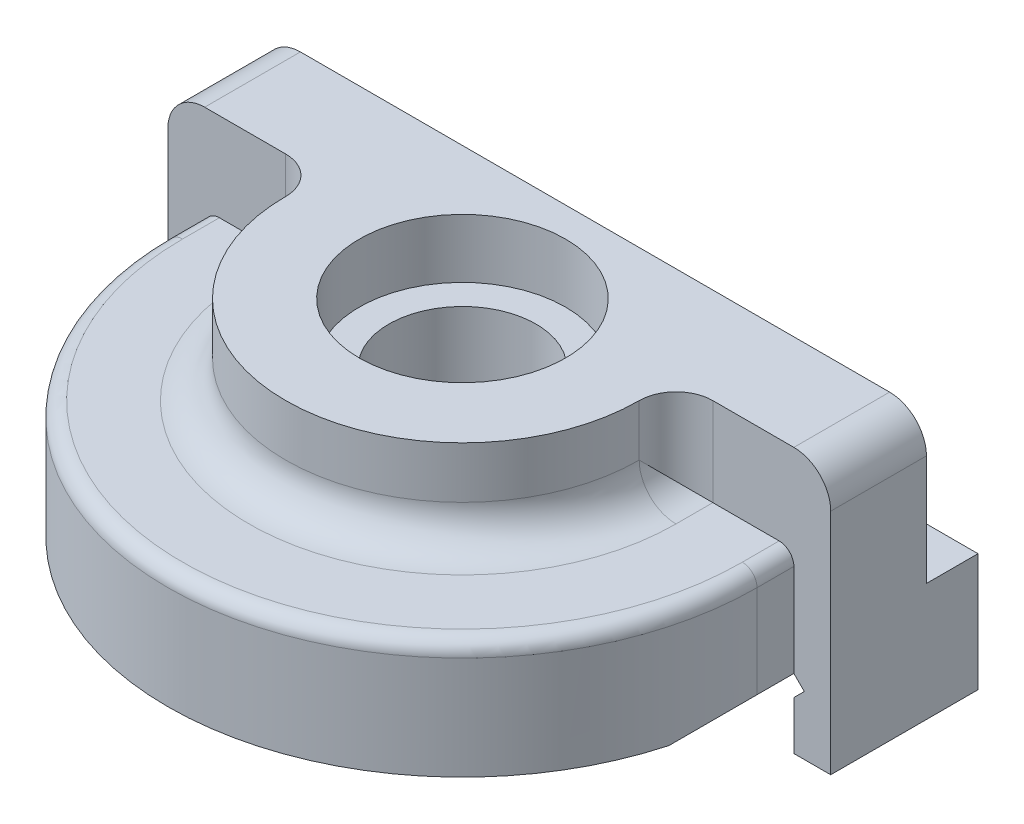
SolidWorks part; units mm, degrees
material "HT200"
ref_plane "前视基准面" through (0, 0, 0) normal (0, 0, 1) x (1, 0, 0)
ref_plane "上视基准面" through (0, 0, 0) normal (0, 1, 0) x (1, 0, 0)
ref_plane "右视基准面" through (0, 0, 0) normal (1, 0, 0) x (0, 0, -1)
sketch "草图1" plane through (0, 0, 0) normal (0, 1, 0) x (1, 0, 0)
  line L0 (0, 63.0153) -> (0, -95.916) construction
  line L1 (-48.6876, 0) -> (44.973, 0) construction
  line L2 (40, 5) -> (-40, 5)
  line L3 (-40, 5) -> (-40, 0)
  line L4 (40, 5) -> (40, 0)
  arc A0 (-40, 0) -> (40, 0) centre (0, 0) ccw
  point P11 (0, 5)
  dimension "D1" = 40
  dimension "D2" = 5
extrude "凸台-拉伸1" add sketch "草图1" along normal blind 16
sketch "草图3" plane through (0, 16, 0) normal (0, 1, 0) x (1, 0, 0)
  line L0 (-24, 5) -> (-24, 0)
  line L1 (40, 5) -> (-40, 5) construction
  line L2 (0, 7.0217) -> (0, -32.5675) construction
  line L3 (24, 5) -> (24, 0)
  line L4 (24, 5) -> (-24, 5)
  arc A0 (-24, 0) -> (24, 0) centre (0, 0) ccw
  dimension "D1" = 24
extrude "凸台-拉伸2" add sketch "草图3" along normal blind 12
sketch "草图4" plane through (0, 0, -5) normal (0, 0, -1) x (-1, 0, 0)
  line L0 (-45, 23) -> (-45, -8)
  line L1 (-45, -8) -> (-40, -8)
  line L2 (-40, 16) -> (-40, 0) construction
  line L3 (-40, 0) -> (-40, -8)
  line L4 (-40.9073, 0.8846) -> (-39.2434, -0.7794) construction
  line L5 (40, 0) -> (40, -8)
  line L6 (0, -3.1778) -> (0, 36.749) construction
  line L7 (45, -8) -> (40, -8)
  line L8 (-40, 0) -> (40, 0)
  line L9 (40, 0) -> (40, 16)
  line L10 (40, 16) -> (24, 16)
  line L11 (24, 16) -> (24, 28)
  line L12 (24, 28) -> (-24, 28)
  line L13 (-24, 28) -> (-24, 16)
  line L14 (-24, 16) -> (-40, 16)
  line L15 (-40, 16) -> (-40, 0)
  line L16 (-40, 0) -> (40, 0)
  line L17 (45, 23) -> (45, -8)
  line L19 (-39.994, -0.8169) -> (-40.006, 0.8169) construction
  line L20 (40, 28) -> (-40, 28)
  arc A0 (45, 23) -> (40, 28) centre (40, 23) ccw
  arc A1 (-45, 23) -> (-40, 28) centre (-40, 23) cw
  point P22 (0, 28)
  point P24 (45, 28)
  point P27 (-45, 28)
  dimension "D4" = 5
  dimension "D2" = 36
  dimension "D3" = 90
  dimension "D1" = 0
extrude "凸台-拉伸3" add sketch "草图4" along normal blind 20
sketch "草图5" plane through (0, 0, -25) normal (0, 0, -1) x (-1, 0, 0)
  line L0 (-45, 8) -> (45, 8)
  line L8 (-40, 0) -> (40, 0)
  line L9 (40, 0) -> (40, -8)
  line L10 (40, -8) -> (45, -8)
  line L11 (45, -8) -> (45, 23)
  line L12 (40, 28) -> (-40, 28)
  line L13 (-45, 23) -> (-45, -8)
  line L14 (-45, -8) -> (-40, -8)
  line L15 (-40, -8) -> (-40, 0)
  line L19 (45, 8) -> (45, 23)
  line L20 (40, 28) -> (-40, 28)
  line L21 (-45, 23) -> (-45, 8)
  arc A2 (45, 23) -> (40, 28) centre (40, 23) ccw
  arc A3 (-40, 28) -> (-45, 23) centre (-40, 23) ccw
  arc A4 (45, 23) -> (40, 28) centre (40, 23) ccw
  arc A5 (-40, 28) -> (-45, 23) centre (-40, 23) ccw
  dimension "D2" = 20
  dimension "D1" = 0
extrude "切除-拉伸1" cut sketch "草图5" against normal blind 7
sketch "草图6" plane through (0, 28, 0) normal (0, 1, 0) x (1, 0, 0)
  circle A0 centre (0, 0) radius 10
  dimension "D1" = 20
extrude "切除-拉伸2" cut sketch "草图6" against normal through all
sketch "草图7" plane through (0, 28, 0) normal (0, 1, 0) x (1, 0, 0)
  circle A0 centre (0, 0) radius 14
  dimension "D1" = 28
extrude "切除-拉伸3" cut sketch "草图7" against normal blind 8
sketch "草图9" plane through (0, 0, -18) normal (0, 0, -1) x (-1, 0, 0)
  line L0 (0, -1.4431) -> (0, 32.2689) construction
  line L1 (-45, 8) -> (45, 8) construction
  point P3 (-20, 19)
  point P4 (20, 19)
  dimension "D1" = 40
  dimension "D2" = 11
hole_wizard "M8 螺纹孔1" positions "草图11" profile "草图10" tap size "M8" standard "GB"
sketch "草图11" plane through (0, 0, -18) normal (0, 0, -1) x (-1, 0, 0)
  point P0 (-20, 19)
  point P1 (20, 19)
sketch "草图10" plane through (20, 19, -18) normal (1, 0, 0) x (0, 1, 0)
  line L0 (0, 0) -> (0, 18.2929)
  line L1 (0, 18.2929) -> (3.4, 16.25)
  line L2 (3.4, 16.25) -> (3.4, 0)
  line L5 (3.4, 0) -> (0, 0)
  line L10 (0, 18.2929) -> (-3.4, 16.25) construction
  line L11 (0, -6.35) -> (0, 107.95) construction
  dimension "螺纹孔钻头直径" = 6.8
  dimension "螺纹孔钻头深度" = 16.25
  dimension "导头角度" = 118
cosmetic thread "孔螺蚊线1" parameters "D1"=10, "D2"=8
cosmetic thread "孔螺蚊线2" parameters "D1"=10, "D2"=8
sketch "草图12" plane through (0, 0, -25) normal (0, 0, -1) x (-1, 0, 0)
  line L0 (-40, 0) -> (-35.1362, -4.8638) construction
  line L1 (-40, 1.4142) -> (-38.5858, 0)
  line L2 (-38.5858, 0) -> (-40, -1.4142)
  line L3 (-40, -1.4142) -> (-41.4142, 0)
  line L4 (-41.4142, 0) -> (-40, 1.4142)
  line L8 (45, 8) -> (-45, 8)
  line L9 (-45, 8) -> (-45, -8)
  line L10 (-45, -8) -> (-40, -8)
  line L11 (-40, -8) -> (-40, 0)
  line L12 (-40, 0) -> (40, 0)
  line L13 (40, 0) -> (40, -8)
  line L14 (40, -8) -> (45, -8)
  line L15 (45, -8) -> (45, 8)
  line L16 (45, 8) -> (-45, 8)
  line L17 (-45, 8) -> (-45, -8)
  line L18 (-45, -8) -> (-40, -8)
  line L19 (-40, -8) -> (-40, 0)
  line L20 (-40, 0) -> (40, 0)
  line L21 (40, 0) -> (40, -8)
  line L22 (40, -8) -> (45, -8)
  line L23 (45, -8) -> (45, 8)
  line M12 (-40, -8) -> (-40, 0)
  line M13 (-40, 0) -> (40, 0)
  dimension "D3" = 2
  dimension "D4" = 2
  dimension "D1" = 0
extrude "切除-拉伸4" cut sketch "草图12" against normal through all contours L4 L3 L1 M12 M13 region at (40.1571, 0.1571, -25)
mirror "镜向1" about plane through (0, 0, 0) normal (1, 0, 0) of "切除-拉伸4"
fillet "圆角3" radius 2 3 edges at (40, 16, -2.5) (0, 16, 40) (-40, 16, -2.5)
fillet "圆角6" radius 5 5 edges at (0, 16, 24)
